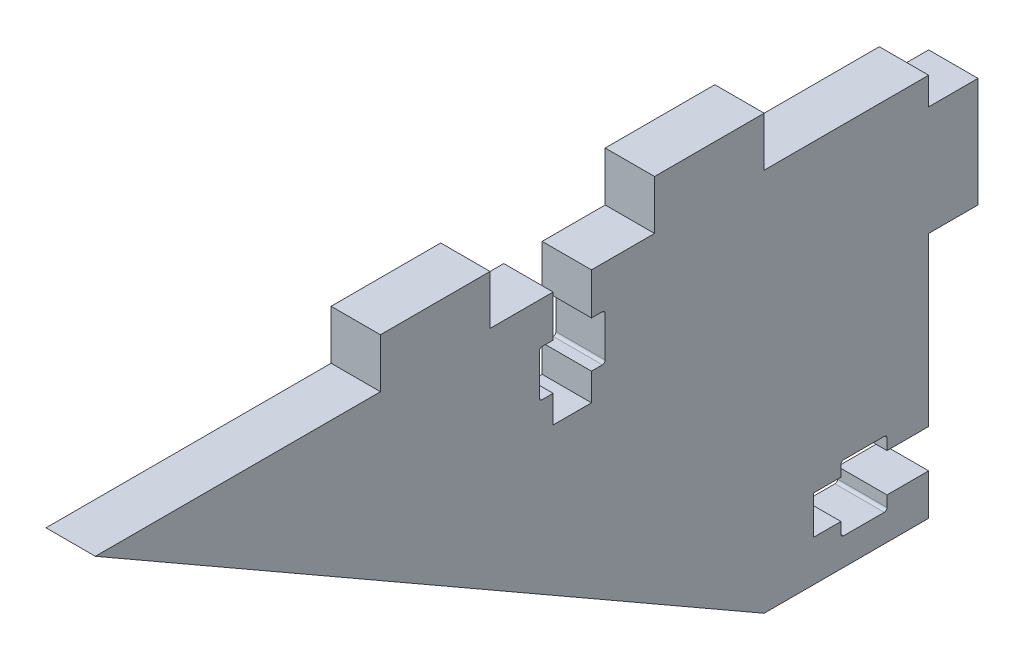
SolidWorks part; units mm, degrees
ref_plane "Front Plane" through (0, 0, 0) normal (0, 0, 1) x (1, 0, 0)
ref_plane "Top Plane" through (0, 0, 0) normal (0, 1, 0) x (1, 0, 0)
ref_plane "Right Plane" through (0, 0, 0) normal (1, 0, 0) x (0, 0, -1)
sketch "Sketch1" plane through (0, 0, 0) normal (1, 0, 0) x (0, 0, -1)
  line L0 (0, 0) -> (0, -35)
  line L1 (0, -35) -> (-76, 0)
  line L2 (-76, 0) -> (0, 0)
  dimension "D1" = 35
  dimension "D2" = 76
extrude "Boss-Extrude1" add sketch "Sketch1" along normal blind 4.5
sketch "Sketch2" plane through (4.5, 0, 0) normal (1, 0, 0) x (0, 0, -1)
  line L0 (0, -35) -> (0, 0) construction
  line L1 (-4.5, -2.5) -> (4.5, -2.5)
  line L2 (-4.5, -2.5) -> (-4.5, -12.5)
  line L3 (-4.5, -12.5) -> (4.5, -12.5)
  line L4 (4.5, -2.5) -> (4.5, -12.5)
  line L5 (-4.5, -2.5) -> (4.5, -12.5) construction
  line L6 (-4.5, -12.5) -> (4.5, -2.5) construction
  line L7 (0, 0) -> (-76, 0) construction
  point P0 (0, -7.5)
  dimension "D2" = 7.5
  dimension "D3" = 4.5
extrude "Boss-Extrude2" add sketch "Sketch2" against normal through all
sketch "Sketch3" plane through (4.5, 0, 0) normal (1, 0, 0) x (0, 0, -1)
  line L0 (0, -35) -> (-15, -35)
  line L1 (0, -25) -> (-76, 0)
  line L4 (0, -35) -> (0, -12.5) construction
  line L5 (0, -25) -> (0, -35)
  line L6 (-76, 0) -> (-15, -35)
  dimension "D1" = 15
  dimension "D2" = 10
extrude "Boss-Extrude3" add sketch "Sketch3" against normal through all
sketch "Sketch4" plane through (4.5, 0, 0) normal (1, 0, 0) x (0, 0, -1)
  line L0 (0, -29.5) -> (-10.5, -29.5) construction
  line L1 (0, -35) -> (0, -12.5) construction
  line L2 (0, -27.75) -> (-10.5, -27.75) construction
  line L3 (-10.5, -27.75) -> (-10.5, -31.25) construction
  line L4 (0, -31.25) -> (0, -27.75)
  line L5 (0, -27.75) -> (-3.8, -27.75)
  line L6 (-3.8, -27.75) -> (-3.8, -26.75)
  line L7 (-4.05, -26.5) -> (-7.75, -26.5)
  line L8 (-8, -26.75) -> (-8, -27.75)
  line L9 (-8, -27.75) -> (-10.5, -27.75)
  line L10 (-10.5, -27.75) -> (-10.5, -31.25)
  line L12 (0, -31.25) -> (-10.5, -31.25) construction
  line L13 (-8, -31.25) -> (-10.5, -31.25)
  line L14 (-8, -32.25) -> (-8, -31.25)
  line L15 (-4.05, -32.5) -> (-7.75, -32.5)
  line L16 (-3.8, -31.25) -> (-3.8, -32.25)
  line L17 (0, -31.25) -> (-3.8, -31.25)
  line L18 (4.5, -12.5) -> (4.5, -2.5) construction
  line L19 (0, -18.5) -> (-43.7571, -18.5) construction
  line L20 (-76, 0) -> (-15, -35) construction
  line L37 (0, -31.25) -> (-10.5, -31.25) construction
  arc A0 (-8, -32.25) -> (-7.75, -32.5) centre (-7.75, -32.25) ccw
  arc A1 (-4.05, -32.5) -> (-3.8, -32.25) centre (-4.05, -32.25) ccw
  arc A2 (-3.8, -26.75) -> (-4.05, -26.5) centre (-4.05, -26.75) ccw
  arc A3 (-7.75, -26.5) -> (-8, -26.75) centre (-7.75, -26.75) ccw
  point P10 (4.5, -7.5)
  point P20 (-8, -32.5)
  point P23 (-3.8, -32.5)
  point P26 (-3.8, -26.5)
  point P29 (-8, -26.5)
  dimension "D7" = 0.25
  dimension "D1" = 10.5
  dimension "D2" = 1.75
  dimension "D3" = 3
  dimension "D4" = 4.2
  dimension "D5" = 8
  dimension "D6" = 22
extrude "Cut-Extrude1" cut sketch "Sketch4" against normal through all
sketch "Sketch5" plane through (4.5, 0, 0) normal (1, 0, 0) x (0, 0, -1)
  line L0 (0, 0) -> (-76, 0) construction
  line L1 (-25, 4.5) -> (-15, 4.5)
  line L2 (-25, 4.5) -> (-25, -4.5)
  line L3 (-25, -4.5) -> (-15, -4.5)
  line L4 (-15, 4.5) -> (-15, -4.5)
  line L5 (-25, 4.5) -> (-15, -4.5) construction
  line L6 (-25, -4.5) -> (-15, 4.5) construction
  line L7 (-32.5, 0) -> (-32.5, 4.5) construction
  line L8 (-40, -4.5) -> (-50, 4.5) construction
  line L9 (-40, 4.5) -> (-50, -4.5) construction
  line L10 (-50, 4.5) -> (-50, -4.5)
  line L11 (-40, -4.5) -> (-50, -4.5)
  line L12 (-40, 4.5) -> (-40, -4.5)
  line L13 (-40, 4.5) -> (-50, 4.5)
  line L14 (-25, -4.5) -> (-15, 4.5) construction
  point P0 (-20, 0)
  point P14 (-45, 0)
  dimension "D3" = 4.5
  dimension "D1" = 20
  dimension "D2" = 10
  dimension "D4" = 25
extrude "Boss-Extrude4" add sketch "Sketch5" against normal through all
sketch "Sketch6" plane through (4.5, 0, 0) normal (1, 0, 0) x (0, 0, -1)
  line L0 (-32.5, 0) -> (-32.5, -10.5) construction
  line L1 (-25, 0) -> (-40, 0) construction
  line L2 (-30.75, -10.5) -> (-34.25, -10.5) construction
  line L3 (-34.25, -10.5) -> (-34.25, 0) construction
  line L4 (-30.75, 0) -> (-34.25, 0)
  line L5 (-34.25, 0) -> (-34.25, -3.8)
  line L6 (-34.25, -3.8) -> (-35.25, -3.8)
  line L7 (-35.5, -4.05) -> (-35.5, -7.75)
  line L8 (-35.25, -8) -> (-34.25, -8)
  line L9 (-34.25, -8) -> (-34.25, -10.5)
  line L10 (-34.25, -10.5) -> (-30.75, -10.5)
  line L11 (-30.75, -10.5) -> (-30.75, 0) construction
  line L12 (-30.75, -8) -> (-30.75, -10.5)
  line L13 (-29.75, -8) -> (-30.75, -8)
  line L14 (-29.5, -4.05) -> (-29.5, -7.75)
  line L15 (-30.75, -3.8) -> (-29.75, -3.8)
  line L16 (-30.75, 0) -> (-30.75, -3.8)
  arc A0 (-35.5, -7.75) -> (-35.25, -8) centre (-35.25, -7.75) ccw
  arc A1 (-35.25, -3.8) -> (-35.5, -4.05) centre (-35.25, -4.05) ccw
  arc A2 (-29.75, -3.8) -> (-29.5, -4.05) centre (-29.75, -4.05) cw
  arc A3 (-29.5, -7.75) -> (-29.75, -8) centre (-29.75, -7.75) cw
  point P12 (-35.5, -8)
  point P15 (-35.5, -3.8)
  point P26 (-29.5, -3.8)
  point P27 (-29.5, -8)
  dimension "D1" = 10.5
  dimension "D2" = 1.75
  dimension "D4" = 4.2
  dimension "D6" = 0.25
  dimension "D3" = 8
  dimension "D5" = 3
extrude "Cut-Extrude2" cut sketch "Sketch6" against normal through all
equation "\"X-ROD-SPACING\"=45"
equation "\"Y-ROD-SPACING\"=75"
equation "\"Z-ROD-SPACING\"=17.5"
equation "\"Y-BED-OFFSET\"=2"
equation "\"Y-BED-ROD-INSET\"=3.5"
equation "\"Y-BED-SCREW-SPACING\"=209"
equation "\"Y-BED-SCREW-CUTOUT-SLOT-HEIGHT\"=1"
equation "\"T-SLOT-NUT-FILLET-RADIUS\"=0.25"
equation "\"T-SLOT-SCREW-SHAFT-RADIUS\"=1.75"
equation "\"T-SLOT-SCREW-SHAFT-CUTOUT-LENGTH\"=10.5"
equation "\"T-SLOT-NUT-DEPTH\"=4.2"
equation "\"T-SLOT-NUT-WIDTH\"=3"
equation "\"T-SLOT-NUT-END-DISTANCE\"=8"
equation "\"ACRYLIC-THICKNESS\"=10"
equation "\"ACRYLIC-THICKNESS2\"=4.5"
equation "\"ACRYLIC-TAB-CUTOUT-SIZE\"=\"ACRYLIC-THICKNESS\"+\"ACRYLIC-TAB-TOLERANCE\"*2"
equation "\"ACRYLIC-TAB-WIDTH\"=\"ACRYLIC-THICKNESS\""
equation "\"ACRYLIC-M3-HOLE\"=3.1"
equation "\"SMOOTHROD-CAP-SCREW-DISTANCE\"=20"
equation "\"FRAME-WIDTH-INNER\"=370"
equation "\"NEMA17-HOLE-SPACING\"=31"
equation "\"NEMA17-CENTRAL-CUTOUT\"=22.5"
equation "\"Z-BRACKET-REACH\"=55"
equation "\"Z-ROD-INSET\"=16"
equation "\"TOP-BRACKET-SPACING\"=40"
equation "\"SMOOTHROD-X-LENGTH\"=350"
equation "\"SMOOTHROD-Y-LENGTH\"=350"
equation "\"SMOOTHROD-Z-LENGTH\"=350"
equation "\"SMOOTHROD-TIGHTENING-HEADROOM\"=1"
equation "\"LEADSCREW-Z-LENGTH\"=300"
equation "\"SCREW-LENGTH-FRAME\"=\"ACRYLIC-THICKNESS\" + 10"
equation "\"SCREW-LENGTH-MOTOR\"=\"ACRYLIC-THICKNESS\" + 5"
equation "\"SCREW-LENGTH-EXTRUDER\"=28"
equation "\"SCREW-HEAD-RADIUS\"=6"
equation "\"PRINTED-X-SMOOTHROD-DIAMETER\"=8.2"
equation "\"PRINTED-X-SMOOTHROD-CUTOUT\"=10"
equation "\"PRINTED-X-BASE-HEIGHT\"=10"
equation "\"PRINTED-LM8UU-CUTOUT-SIZE\"=15.25"
equation "\"PRINTED-LM8UU-CUTOUT-LENGTH\"=24.5"
equation "\"PRINTED-X-IDLER-HEIGHT\"=16"
equation "\"PSU-MOUNTING-WIDTH\"=95"
equation "\"PSU-MOUNTING-HEIGHT\"=177"
equation "\"Y-BELT-TO-ROD-DISTANCE\"=20"
equation "\"SPOOL-HOLDER-ROD-SPACING\"=150"
equation "\"ACRYLIC-X-CARRIAGE-WIDTH\"=55"
equation "\"ACRYLIC-X-CARRIAGE-HEIGHT\"=75"
equation "\"ACRYLIC-X-CARRIAGE-SCREW-SPACING-X\"=15"
equation "\"ACRYLIC-X-CARRIAGE-SCREW-SPACING-Y\"=33"
equation "\"ACRYLIC-X-CARRIAGE-CENTER-TAB-SPACING\"=14"
equation "\"ACRYLIC-X-CARRIAGE-EXTRUDER-SHELF-DEPTH\"=\"ACRYLIC-X-CARRIAGE-EXTRUDER-OFFSET\" + 30"
equation "\"D1@Boss-Extrude1\"=\"ACRYLIC-THICKNESS2\""
equation "\"D1@Sketch2\"=\"ACRYLIC-TAB-WIDTH\""
equation "\"D3@Sketch2\"=\"ACRYLIC-THICKNESS2\""
equation "\"ACRYLIC-X-CARRIAGE-LM8UU-CUTOUT-WIDTH\"=24.25"
equation "\"ACRYLIC-X-CARRIAGE-EXTRUDER-BRACE-SPACING\"=23"
equation "\"ACRYLIC-X-CARRIAGE-EXTRUDER-BRACE-HEIGHT\"=35"
equation "\"D1@Sketch1\"=\"ACRYLIC-X-CARRIAGE-EXTRUDER-BRACE-HEIGHT\""
equation "\"D1@Sketch4\"=\"T-SLOT-SCREW-SHAFT-CUTOUT-LENGTH\""
equation "\"D2@Sketch4\"=\"T-SLOT-SCREW-SHAFT-RADIUS\""
equation "\"D3@Sketch4\"=\"T-SLOT-NUT-WIDTH\""
equation "\"D4@Sketch4\"=\"T-SLOT-NUT-DEPTH\""
equation "\"D5@Sketch4\"=\"T-SLOT-NUT-END-DISTANCE\""
equation "\"D7@Sketch4\"=\"T-SLOT-NUT-FILLET-RADIUS\""
equation "\"ACRYLIC-X-CARRIAGE-EXTRUDER-BRACE-SCREW-SPACING\"=22"
equation "\"D6@Sketch4\"=\"ACRYLIC-X-CARRIAGE-EXTRUDER-BRACE-SCREW-SPACING\""
equation "\"ACRYLIC-X-CARRIAGE-EXTRUDER-BRACE-TAB-OFFSET\"=20"
equation "\"D1@Sketch5\"=\"ACRYLIC-X-CARRIAGE-EXTRUDER-BRACE-TAB-OFFSET\""
equation "\"D2@Sketch5\"=\"ACRYLIC-TAB-WIDTH\""
equation "\"D3@Sketch5\"=\"ACRYLIC-THICKNESS2\""
equation "\"ACRYLIC-X-CARRIAGE-EXTRUDER-OFFSET\"=26"
equation "\"ACRYLIC-X-CARRIAGE-EXTRUDER-ANGLE\"=90"
equation "\"D1@Sketch6\"=\"T-SLOT-SCREW-SHAFT-CUTOUT-LENGTH\""
equation "\"D2@Sketch6\"=\"T-SLOT-SCREW-SHAFT-RADIUS\""
equation "\"D3@Sketch6\"=\"T-SLOT-NUT-END-DISTANCE\""
equation "\"D4@Sketch6\"=\"T-SLOT-NUT-DEPTH\""
equation "\"D5@Sketch6\"=\"T-SLOT-NUT-WIDTH\""
equation "\"D6@Sketch6\"=\"T-SLOT-NUT-FILLET-RADIUS\""
